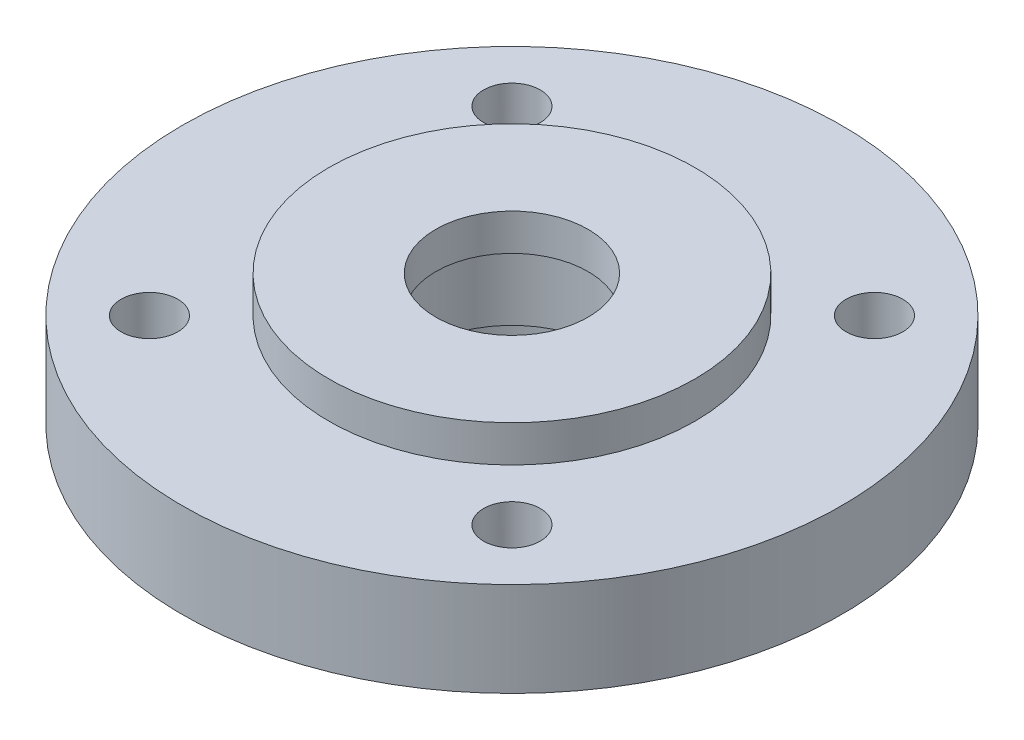
SolidWorks part; units mm, degrees
material "6061-T6 (SS)"
ref_plane "Front Plane" through (0, 0, 0) normal (0, 0, 1) x (1, 0, 0)
ref_plane "Top Plane" through (0, 0, 0) normal (0, 1, 0) x (1, 0, 0)
ref_plane "Right Plane" through (0, 0, 0) normal (1, 0, 0) x (0, 0, -1)
sketch "Sketch1" plane through (0, 0, 0) normal (0, 0, 1) x (1, 0, 0)
  line L0 (0, 0) -> (0, -62.4802) construction
  line L3 (-15.875, -62.4802) -> (-6.604, -62.4802)
  line L4 (-6.604, -62.4802) -> (-6.604, -65.6552)
  line L5 (-6.604, -65.6552) -> (-7.9375, -65.6552)
  line L6 (-7.9375, -65.6552) -> (-7.9375, -72.0052)
  line L7 (-15.875, -62.4802) -> (-15.875, -65.6552)
  line L8 (-15.875, -65.6552) -> (-28.575, -65.6552)
  line L9 (-28.575, -65.6552) -> (-28.575, -73.8302)
  line L10 (-7.9375, -72.0052) -> (-9.5, -72.0052)
  line L12 (76.2, -73.8302) -> (-76.2, -73.8302) construction
  line L14 (-14.2875, -73.8302) -> (-14.2875, -77.0052)
  line L15 (-14.2875, -77.0052) -> (-9.5, -77.0052)
  line L16 (-9.5, -77.0052) -> (-9.5, -72.0052)
  line L17 (-28.575, -73.8302) -> (-19.05, -73.8302)
  line L18 (-19.05, -73.8302) -> (-19.05, -70.6933)
  line L19 (-19.05, -70.6933) -> (-14.2875, -70.6933)
  line L20 (-14.2875, -70.6933) -> (-14.2875, -73.8302)
  dimension "D1" = 13.208
  dimension "D2" = 19
  dimension "D3" = 15.875
  dimension "D4" = 3.175
  dimension "D5" = 3.175
  dimension "D6" = 12.7
  dimension "D7" = 57.15
  dimension "D8" = 6.35
  dimension "D9" = 28.575
  dimension "D10" = 5
  dimension "D11" = 3.175
  dimension "D12" = 38.1
  dimension "D13" = 3.1369
revolve "Revolve1" add sketch "Sketch1" angle 360 about L0
hole_wizard "#10 (0.1935) Diameter Hole1" positions "Sketch2" profile "Sketch3" hole size "#10" standard "ANSI Inch" end condition through all
sketch "Sketch2" plane through (0, -62.4802, 0) normal (0, 1, 0) x (1, 0, 0)
  line L0 (-15.7154, 15.7154) -> (15.7154, -15.7154) construction
  line L2 (15.7154, 15.7154) -> (-15.7154, -15.7154) construction
  line L3 (0, 0) -> (-24.7223, 0) construction
  point P0 (15.7154, 15.7154)
  point P2 (-15.7154, 15.7154)
  point P4 (-15.7154, -15.7154)
  point P6 (15.7154, -15.7154)
  dimension "D1" = 44.45
  dimension "D2" = 45
sketch "Sketch3" plane through (15.7154, -62.4802, -15.7154) normal (1, 0, 0) x (0, 0, 1)
  line L0 (0, 0) -> (0, 14.525)
  line L1 (0, 14.525) -> (2.4574, 14.525)
  line L2 (2.4574, 14.525) -> (2.4574, 0)
  line L5 (2.4574, 0) -> (0, 0)
  line L11 (0, -6.35) -> (0, 107.95) construction
  dimension "Thru Hole Dia." = 4.9149
  dimension "Thru Hole Depth" = 14.525
